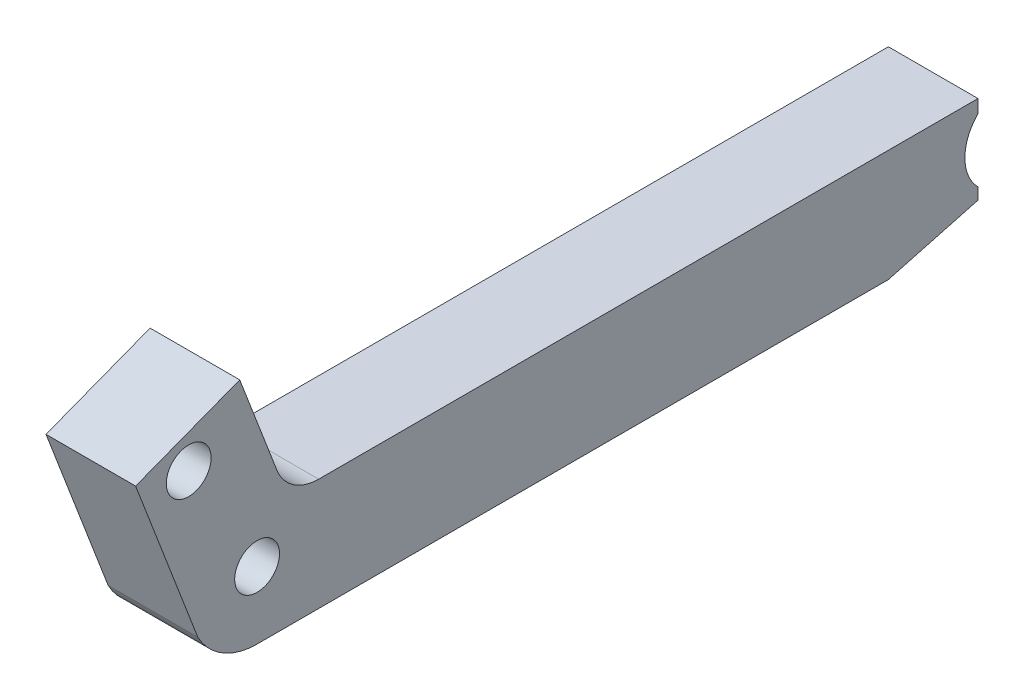
SolidWorks part; units mm, degrees
ref_plane "前基準面" through (0, 0, 0) normal (0, 0, 1) x (1, 0, 0)
ref_plane "上基準面" through (0, 0, 0) normal (0, 1, 0) x (1, 0, 0)
ref_plane "右基準面" through (0, 0, 0) normal (1, 0, 0) x (0, 0, -1)
ref_axis "基準軸1" through (0, -55, 0) along (0, 1, 0)
ref_axis "基準軸2" through (-88.99, 0, 0) along (1, 0, 0)
ref_axis "基準軸3" through (0, 0, 55) along (0, 0, -1)
sketch "草圖1" plane through (0, 0, 0) normal (1, 0, 0) x (0, 0, -1)
  line L0 (0, -7.5) -> (80.4364, -7.5)
  line L1 (80.4364, -7.5) -> (80.4364, -3.5355)
  line L2 (80.4364, 5) -> (3.4364, 5)
  line L3 (80.4364, 5) -> (80.4364, 3.5355)
  line L4 (55, 0) -> (-55, 0) construction
  line L5 (3.4364, 5) -> (-1.9391, 19.0037)
  line L6 (-1.9391, 19.0037) -> (-13.5548, 14.5448)
  line L7 (-13.5548, 14.5448) -> (-6.6146, -3.5351)
  line L8 (0, 55) -> (0, -55) construction
  circle A0 centre (0, 0) radius 2.5
  arc A1 (-6.6146, -3.5351) -> (0, -7.5) centre (0, 0) ccw
  arc A2 (80.4364, 3.5355) -> (80.4364, -3.5355) centre (83.9719, 0) ccw
  dimension "D1" = 5
  dimension "D2" = 15
  dimension "D4" = 5
  dimension "D3" = 15
  dimension "D5" = 90
  dimension "D6" = 111
  dimension "D7" = 12.4421
  dimension "D8" = 77
  dimension "D9" = 5
  dimension "D10" = 3.4364
extrude "填料-伸長1" add sketch "草圖1" along normal blind 10
fillet "圓角1" radius 5 1 edges at (5, 5, -3.4364)
sketch "草圖2" plane through (0, 0, 0) normal (-1, 0, 0) x (0, 0, 1)
  line L0 (13.5548, 14.5448) -> (6.6146, -3.5351) construction
  line L1 (1.9391, 19.0037) -> (13.5548, 14.5448) construction
  circle A0 centre (7.6327, 13.0692) radius 2.5
  dimension "D3" = 5
  dimension "D1" = 5
  dimension "D2" = 3.5
extrude "除料-伸長1" cut sketch "草圖2" against normal up to next
chamfer "導角1" distance 10 angle 15 1 edges at (5, -7.5, -80.4364) first distance on face at (5, -7.5, -40.2182)
